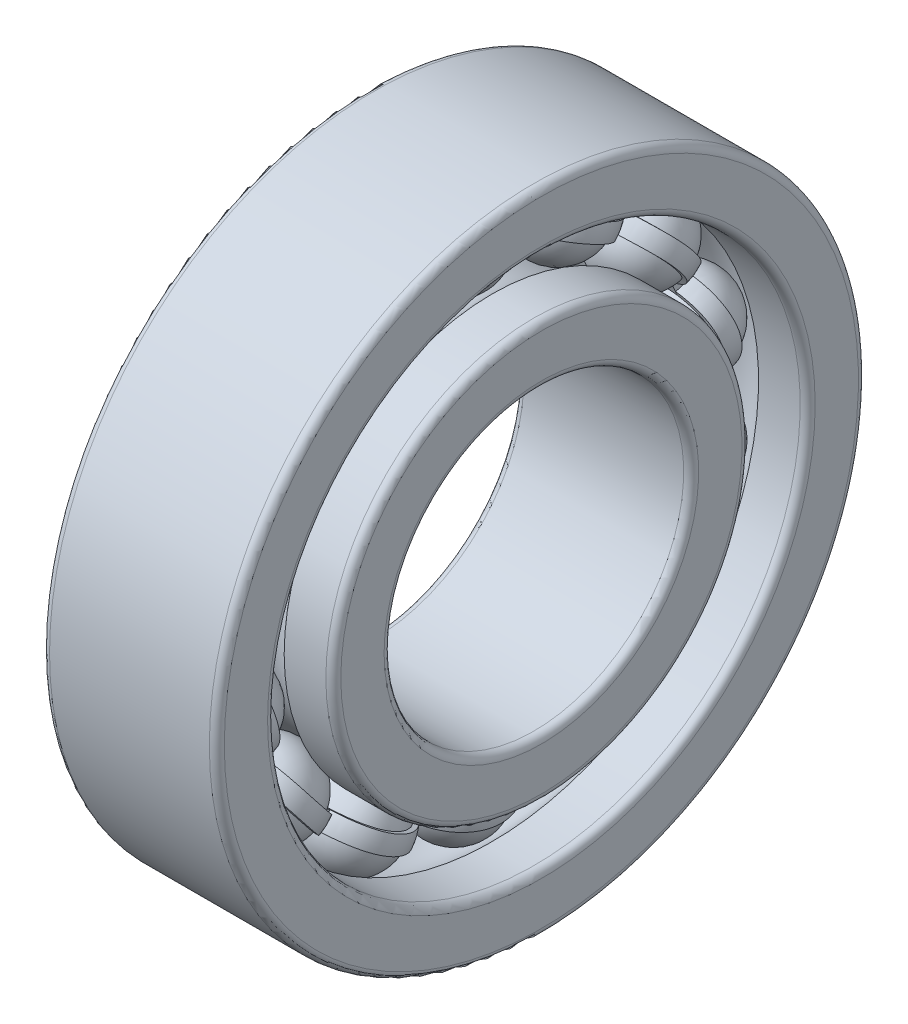
SolidWorks part; units mm, degrees
material "AISI 304"
ref_plane "前视基准面" through (0, 0, 0) normal (0, 0, 1) x (1, 0, 0)
ref_plane "上视基准面" through (0, 0, 0) normal (0, 1, 0) x (1, 0, 0)
ref_plane "右视基准面" through (0, 0, 0) normal (1, 0, 0) x (0, 0, -1)
sketch "尺寸草图" plane through (0, 0, 0) normal (0, 0, 1) x (1, 0, 0)
  line L0 (-19.9271, 0) -> (19.9271, 0) construction
  line L1 (0, 21.603) -> (0, -21.603) construction
  line L2 (-1.6, 6.5) -> (1.6, 6.5)
  line L3 (1.75, 6.35) -> (1.75, 5.4833)
  line L4 (-1.75, 6.35) -> (-1.75, 5.4833)
  line L5 (-1.6, 5.3333) -> (1.6, 5.3333)
  line L6 (-3.5, 4.75) -> (3.3577, 4.75) construction
  line L7 (-1.6, 4.1667) -> (1.6, 4.1667)
  line L8 (1.75, 4.0167) -> (1.75, 3.15)
  line L9 (1.6, 3) -> (-1.6, 3)
  line L10 (-1.75, 3.15) -> (-1.75, 4.0167)
  line L11 (0, 4.75) -> (0, 5.625) construction
  circle A0 centre (0, 4.75) radius 0.875
  arc A1 (1.75, 5.4833) -> (1.6, 5.3333) centre (1.6, 5.4833) cw
  arc A2 (1.75, 4.0167) -> (1.6, 4.1667) centre (1.6, 4.0167) ccw
  arc A3 (-1.6, 4.1667) -> (-1.75, 4.0167) centre (-1.6, 4.0167) ccw
  arc A4 (-1.6, 5.3333) -> (-1.75, 5.4833) centre (-1.6, 5.4833) cw
  arc A5 (-1.6, 3) -> (-1.75, 3.15) centre (-1.6, 3.15) cw
  arc A6 (1.6, 3) -> (1.75, 3.15) centre (1.6, 3.15) ccw
  arc A7 (1.75, 6.35) -> (1.6, 6.5) centre (1.6, 6.35) ccw
  arc A8 (-1.6, 6.5) -> (-1.75, 6.35) centre (-1.6, 6.35) ccw
  point P7 (0, 0)
  point P25 (-1.75, 4.1667)
  point P28 (-1.75, 5.3333)
  point P31 (-1.75, 3)
  point P36 (1.75, 6.5)
  point P39 (-1.75, 6.5)
  dimension "D1" = 0.2917
  dimension "D3" = 0.15
  dimension "B" = 3.5
  dimension "D2" = 1.75
  dimension "D" = 13
  dimension "(d)" = 6
  dimension "D5" = 4.75
  dimension "D6" = 1.1667
  dimension "D7" = 1.1667
sketch "草图2" plane through (0, 0, 0) normal (0, 0, 1) x (1, 0, 0)
  line L6 (1.6, 3) -> (-1.6, 3) construction
  line L8 (-1.75, 6.35) -> (-1.75, 5.4833) construction
  line L9 (-1.6, 5.3333) -> (1.6, 5.3333) construction
  line L10 (-1.6, 6.5) -> (1.6, 6.5) construction
  line L11 (1.75, 6.35) -> (1.75, 5.4833) construction
  line L12 (1.75, 4.0167) -> (1.75, 3.15) construction
  line L13 (-1.6, 4.1667) -> (1.6, 4.1667) construction
  line L14 (1.6, 3) -> (-1.6, 3)
  line L15 (-1.75, 3.15) -> (-1.75, 4.0167) construction
  line L18 (-3.5, 0) -> (3.5, 0) construction
  line L19 (-19.9271, 0) -> (19.9271, 0) construction
  line L20 (-1.75, 6.35) -> (-1.75, 5.4833)
  line L21 (-1.6, 5.3333) -> (-0.6522, 5.3333)
  line L22 (-1.6, 6.5) -> (1.6, 6.5)
  line L23 (1.75, 6.35) -> (1.75, 5.4833)
  line L24 (1.75, 4.0167) -> (1.75, 3.15)
  line L25 (-1.6, 4.1667) -> (-0.6522, 4.1667)
  line L26 (-1.75, 3.15) -> (-1.75, 4.0167)
  line L27 (0.6522, 5.3333) -> (1.6, 5.3333)
  line L28 (0.6522, 4.1667) -> (1.6, 4.1667)
  circle A0 centre (0, 4.75) radius 0.875 construction
  arc A1 (0.6522, 5.3333) -> (-0.6522, 5.3333) centre (0, 4.75) ccw
  arc A2 (-0.6522, 4.1667) -> (0.6522, 4.1667) centre (0, 4.75) ccw
  arc A3 (-1.6, 6.5) -> (-1.75, 6.35) centre (-1.6, 6.35) ccw construction
  arc A4 (-1.75, 5.4833) -> (-1.6, 5.3333) centre (-1.6, 5.4833) ccw construction
  arc A5 (1.75, 6.35) -> (1.6, 6.5) centre (1.6, 6.35) ccw construction
  arc A6 (1.6, 5.3333) -> (1.75, 5.4833) centre (1.6, 5.4833) ccw construction
  arc A7 (1.75, 4.0167) -> (1.6, 4.1667) centre (1.6, 4.0167) ccw construction
  arc A8 (1.6, 3) -> (1.75, 3.15) centre (1.6, 3.15) ccw construction
  arc A9 (-1.6, 4.1667) -> (-1.75, 4.0167) centre (-1.6, 4.0167) ccw construction
  arc A10 (-1.75, 3.15) -> (-1.6, 3) centre (-1.6, 3.15) ccw construction
  arc A11 (-1.6, 6.5) -> (-1.75, 6.35) centre (-1.6, 6.35) ccw
  arc A12 (-1.75, 5.4833) -> (-1.6, 5.3333) centre (-1.6, 5.4833) ccw
  arc A13 (1.75, 6.35) -> (1.6, 6.5) centre (1.6, 6.35) ccw
  arc A14 (1.6, 5.3333) -> (1.75, 5.4833) centre (1.6, 5.4833) ccw
  arc A15 (1.75, 4.0167) -> (1.6, 4.1667) centre (1.6, 4.0167) ccw
  arc A16 (1.6, 3) -> (1.75, 3.15) centre (1.6, 3.15) ccw
  arc A17 (-1.6, 4.1667) -> (-1.75, 4.0167) centre (-1.6, 4.0167) ccw
  arc A18 (-1.75, 3.15) -> (-1.6, 3) centre (-1.6, 3.15) ccw
revolve "旋转1" add sketch "草图2" angle 360 about L18
sketch "草图5" plane through (0, 0, 0) normal (0, 0, 1) x (1, 0, 0)
  line L1 (-0.2625, 4.575) -> (0.2625, 4.575)
  line L2 (-0.2625, 4.575) -> (-0.2625, 4.925)
  line L3 (-0.2625, 4.925) -> (0.2625, 4.925)
  line L4 (0.2625, 4.575) -> (0.2625, 4.925)
  line L5 (-0.2625, 4.575) -> (0.2625, 4.925) construction
  line L6 (-0.2625, 4.925) -> (0.2625, 4.575) construction
  circle A0 centre (0, 4.75) radius 0.875 construction
  circle A1 centre (0, 4.75) radius 0.875 construction
  point P0 (0, 4.75)
  dimension "D1" = 0.525
  dimension "D2" = 0.35
revolve "旋转3" add sketch "草图5" angle 360 about L0
ref_axis "基准轴1" through (-3.85, 0, 0) along (1, 0, 0)
sketch "草图3" plane through (0, 0, 0) normal (0, 0, 1) x (1, 0, 0)
  line L1 (-0.9625, 4.75) -> (0.9625, 4.75)
  circle A0 centre (0, 4.75) radius 0.875 construction
  circle A1 centre (0, 4.75) radius 0.875 construction
  arc A2 (0.9625, 4.75) -> (-0.9625, 4.75) centre (0, 4.75) ccw
  dimension "D2" = 1.925
revolve "旋转2" add sketch "草图3" angle 360 about L1 region at (0, 5.1585, 0)
pattern_circular "阵列(圆周)5" count 14 over 360 about axis through (-3.85, 0, 0) along (1, 0, 0) of bodies 103
sketch "草图6" plane through (0, 0, 0) normal (0, 0, 1) x (1, 0, 0)
  line L0 (-0.9465, 4.925) -> (0.9465, 4.925)
  line L1 (-3.5, 4.75) -> (1.75, 4.75) construction
  line L3 (-0.9465, 4.575) -> (0.9465, 4.575)
  line L4 (1.75, -6.35) -> (1.75, 6.35) construction
  arc A0 (-0.9465, 4.575) -> (0.9465, 4.575) centre (0, 4.75) ccw
  circle A1 centre (0, 4.75) radius 0.875 construction
  circle A2 centre (0, 4.75) radius 0.875 construction
  arc A3 (0.9465, 4.925) -> (-0.9465, 4.925) centre (0, 4.75) ccw
  dimension "D1" = 1.925
  dimension "D3" = 0.175
  dimension "D4" = 0.175
revolve "切除-旋转1" cut sketch "草图6" angle 360 about L0
sketch "草图7" plane through (0, 0, 0) normal (0, 0, 1) x (1, 0, 0)
  line L0 (-0.875, 4.75) -> (0.875, 4.75)
  line L1 (-1.75, 0) -> (1.75, 0) construction
  line L2 (-1.75, 6.35) -> (-1.75, -6.35) construction
  line L3 (1.75, -6.35) -> (1.75, 6.35) construction
  circle A0 centre (0, 4.75) radius 0.875 construction
  arc A1 (0.875, 4.75) -> (-0.875, 4.75) centre (0, 4.75) ccw
revolve "旋转4" add sketch "草图7" angle 360 about L0
pattern_circular "阵列(圆周)2" count 14 over 360 about axis through (-3.85, 0, 0) along (1, 0, 0) of "旋转4"
